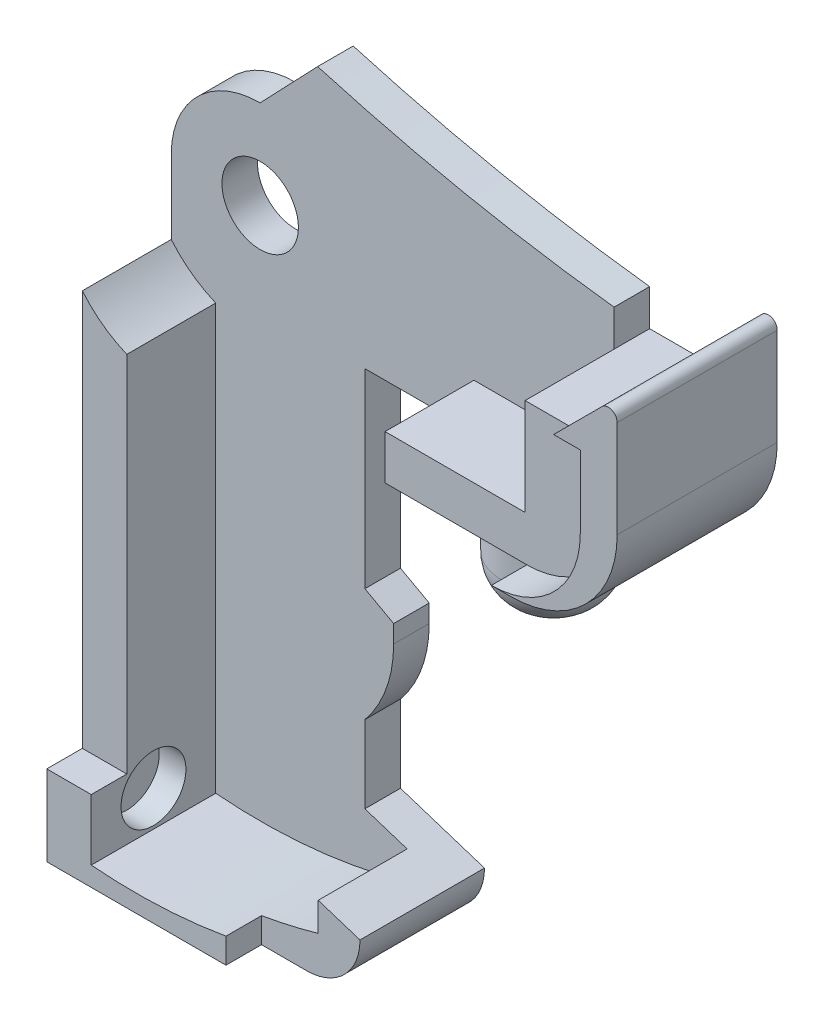
SolidWorks part; units mm, degrees
ref_plane "정면" through (0, 0, 0) normal (0, 0, 1) x (1, 0, 0)
ref_plane "윗면" through (0, 0, 0) normal (0, 1, 0) x (1, 0, 0)
ref_plane "우측면" through (0, 0, 0) normal (1, 0, 0) x (0, 0, -1)
sketch "스케치1" plane through (0, 0, 0) normal (0, 0, 1) x (1, 0, 0)
  line L0 (0, 5) -> (3.2319, 8.3833)
  line L1 (0, 5) -> (19.9, 5)
  line L2 (19.9, 5) -> (19.9, 2.9507)
  line L3 (19.9, 2.9507) -> (23.5, 2.9507)
  line L4 (23.5, 2.9507) -> (23.5, 4.0959)
  line L5 (23.5, 4.0959) -> (25, 4.0959)
  line L6 (25, 4.0959) -> (25, 0)
  line L7 (20, -5) -> (5.8894, -5)
  line L8 (5.8894, -5) -> (5.8894, -26.4376)
  line L9 (-5, -30.9618) -> (7.6137, -30.9618)
  line L10 (-5, -30.9618) -> (-5, 0)
  line L14 (19.9, 2.9507) -> (19.9, -2.4993)
  line L15 (19.9, -2.4993) -> (12.0232, -2.4993)
  line L16 (-2.5, -4.3301) -> (-2.5, -26.4377)
  line L17 (-2.5, -29.8745) -> (-2.5, -26.4377)
  line L18 (-2.5, -26.4377) -> (-5, -26.4377)
  line L19 (5.0761, -29.546) -> (5.0761, -30.9618)
  line L20 (5.8894, -15.7188) -> (5.8894, -26.4376)
  line L21 (8.2649, -27.204) -> (8.2649, -28.8171)
  line L22 (12.0232, -2.4993) -> (12.0232, -5)
  line L23 (5.8894, -15.7188) -> (5.8894, -26.4376)
  line L24 (7.5062, -17.6039) -> (7.5062, -16.6061)
  line L25 (7.5062, -16.6061) -> (5.8894, -15.7188)
  line L26 (23.5, 4.0959) -> (26.2222, 6.8181)
  line L27 (27.0757, 6.4645) -> (27.0757, 1)
  line L28 (21.0757, -5) -> (20, -5)
  line L29 (10.6137, -27.9618) -> (5.8894, -26.4376)
  circle A0 centre (0, 0) radius 2.15
  circle A1 centre (0, 0) radius 5
  arc A2 (-2.5, -29.8745) -> (8.2649, -28.8171) centre (0, 0) ccw
  arc A3 (-5, -4.1533) -> (-2.5, -6) centre (0, 0) ccw
  arc A4 (19.9, 5) -> (3.2319, 8.3833) centre (32.0341, 107.5303) cw
  arc A5 (25, 0) -> (20, -5) centre (20, 0) cw
  arc A6 (7.5062, -17.6039) -> (5.8894, -22.0908) centre (0.4717, -17.6039) cw
  arc A7 (7.6137, -30.9618) -> (10.6137, -27.9618) centre (7.6137, -27.9618) ccw
  arc A8 (27.0757, 1) -> (21.0757, -5) centre (21.0757, 1) cw
  arc A9 (26.2222, 6.8181) -> (27.0757, 6.4645) centre (26.5757, 6.4645) cw
  point P48 (27.0757, 7.6716)
  dimension "D1" = 4.3
  dimension "D2" = 2.5
  dimension "D3" = 5
  dimension "D6" = 3
  dimension "D9" = 6
  dimension "D10" = 0.5
  dimension "D4" = 30
  dimension "D5" = 1.5
  dimension "D7" = 5.0568
  dimension "D8" = 45
  dimension "D11" = 3.6
  dimension "D12" = 32.0757
  dimension "D13" = 5.45
extrude "보스-돌출3" add sketch "스케치1" along normal blind 9 contours A2 L17 L18 L10 L9 L19 | A9 L26 L5 L6 A5 L28 A8 L27 region at (-3.75, -26.5481, 0) region at (25.5751, 1.3496, 0)
extrude "보스-돌출4" add sketch "스케치1<7>" along normal blind 7 contours A2 L19 L9 | L15 L7 L6 L5 L4 L3 L14 | A1 L10 L18 L16 region at (20.1107, -1.564, 0) region at (-3.7678, -15.8289, 0) region at (8.0449, -29.4837, 0)
sketch "스케치1<7>" plane through (0, 0, 0) normal (0, 0, 1) x (1, 0, 0) same geometry as "스케치1"
extrude "보스-돌출5" add sketch "스케치1<8>" along normal blind 2 contours L17 A2 L8 L15 L14 L2 L1 A1 L10 L18 | A1 A0 | L10 A3 L16 A1 | L1 A4 L0 | A6 L23 region at (7.1976, 6.0706, 0) region at (5.558, -10.4695, 0) region at (3.4355, 3.4355, 0) region at (-3.8947, -3.9886, 0) region at (6.5659, -18.5308, 0)
sketch "스케치1<8>" plane through (0, 0, 0) normal (0, 0, 1) x (1, 0, 0) same geometry as "스케치1"
sketch "스케치2" plane through (0, -5, 0) normal (0, -1, 0) x (1, 0, 0)
  circle A0 centre (18, 3.5) radius 2.9
  dimension "D1" = 5.8
extrude "보스-돌출6" add sketch "스케치2" along normal mid plane 4.9
sketch "스케치4" plane through (0, -7.45, 0) normal (0, -1, 0) x (1, 0, 0)
  circle A0 centre (18, 3.5) radius 2.9 construction
  circle A1 centre (18, 3.5) radius 2.9
extrude "보스-돌출7" add sketch "스케치4" along normal blind 2
fillet "필렛2" radius 2.4 1 edges at (18, -9.45, 0.6)
sketch "스케치5" plane through (-2.5, 0, 0) normal (1, 0, 0) x (0, 0, -1)
  line L0 (-9, -29.8745) -> (-2, -29.8745) construction
  circle A0 centre (-5.5, -27.8745) radius 1.825
  point P2 (-5.5, -29.8745)
  dimension "D1" = 3.65
  dimension "D2" = 2
extrude "컷-돌출1" cut sketch "스케치5" against normal blind 1.5
